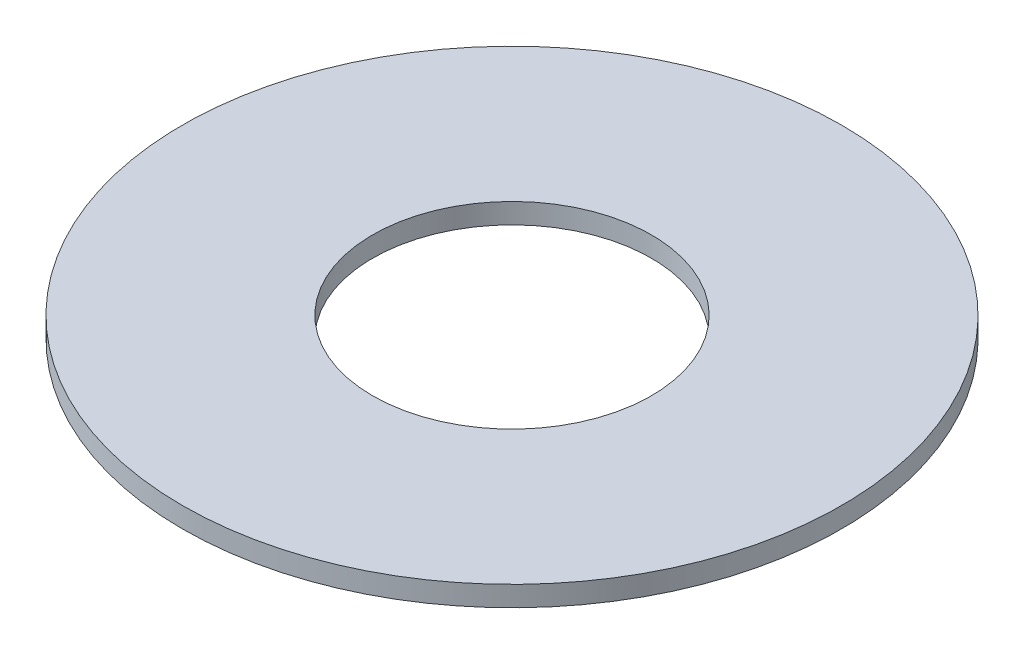
SolidWorks part; units mm, degrees
ref_plane "Front Plane" through (0, 0, 0) normal (0, 0, 1) x (1, 0, 0)
ref_plane "Top Plane" through (0, 0, 0) normal (0, 1, 0) x (1, 0, 0)
ref_plane "Right Plane" through (0, 0, 0) normal (1, 0, 0) x (0, 0, -1)
sketch "Sketch1" plane through (0, 0, 0) normal (0, 1, 0) x (1, 0, 0)
  circle A0 centre (0, 0) radius 65
  dimension "FLANGE_OD" = 130
extrude "Boss-Extrude1" add sketch "Sketch1" along normal blind 4
sketch "Sketch2" plane through (0, 0, 0) normal (0, 1, 0) x (1, 0, 0)
  circle A0 centre (0, 0) radius 27.5
  dimension "BORE_D" = 55
extrude "Cut-Extrude1" cut sketch "Sketch2" along normal through all
sketch "Sketch3" plane through (0, 4, 0) normal (0, 1, 0) x (1, 0, 0)
  circle A0 centre (0, 0) radius 18.1707 construction
  circle A1 centre (-18.1707, 0) radius 6.1066
  dimension "BOLT_D" = 12.2132
  dimension "BOLT_PCD" = 36.3413
extrude "Cut-Extrude2" cut sketch "Sketch3" against normal blind 3.2262 rebuild error yes
pattern_circular "CirPattern1" count 4 over 360 rebuild error yes
